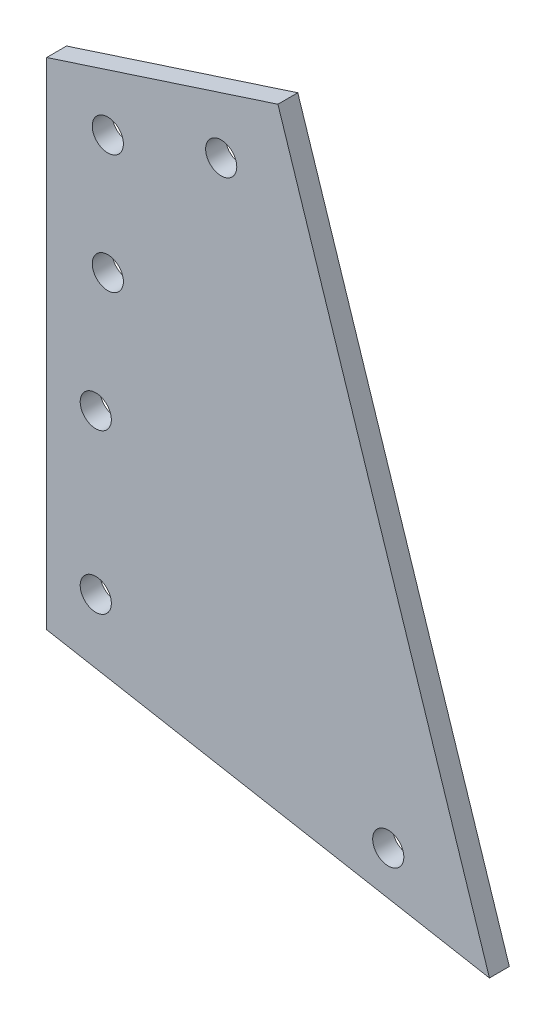
SolidWorks part; units mm, degrees
material "6061 Alloy"
ref_plane "Front Plane" through (0, 0, 0) normal (0, 0, 1) x (1, 0, 0)
ref_plane "Top Plane" through (0, 0, 0) normal (0, 1, 0) x (1, 0, 0)
ref_plane "Right Plane" through (0, 0, 0) normal (1, 0, 0) x (0, 0, -1)
sketch "Sketch2" plane through (0, 0, 0) normal (0, 0, 1) x (1, 0, 0)
  line L0 (40.9906, 297.6036) -> (41.8047, 295.0986) construction
  line L2 (40.9906, 297.6036) -> (52.5693, 261.9727) construction
  line L6 (197.5978, -184.3191) -> (40.9906, 297.6036) construction
  line L7 (75.6055, 191.0842) -> (41.8047, 295.0986)
  line L8 (4.8542, 283.091) -> (4.8542, 203.9015)
  line L9 (4.8542, 203.9015) -> (75.6055, 191.0842)
  line L10 (12.7, 238.125) -> (12.7, 212.725) construction
  line L11 (52.3134, 180.5741) -> (64.7523, 184.6158) construction
  line L12 (173.4413, -192.1691) -> (25.4, 263.394) construction
  line L13 (64.7523, 184.6158) -> (29.6, 292.8012) construction
  line L14 (41.8047, 295.0986) -> (4.8542, 283.091)
  dimension "D1" = 109.3686
extrude "Boss-Extrude1" add sketch "Sketch2" along normal blind 3.175
sketch "Sketch3" plane through (0, 0, 3.175) normal (0, 0, 1) x (1, 0, 0)
  line L0 (75.6055, 191.0842) -> (63.8877, 187.2769) construction
  line L1 (63.8877, 187.2769) -> (29.6006, 292.8015) construction
  line L3 (61.8403, 193.5779) -> (59.4352, 200.9803) construction
  line L4 (4.8542, 203.9015) -> (75.6055, 191.0842) construction
  line L5 (29.6006, 292.8015) -> (32.7403, 283.1387) construction
  line L6 (32.7403, 283.1387) -> (14.6226, 277.2519) construction
  line L7 (14.6226, 277.2519) -> (14.6226, 258.2019) construction
  dimension "D1" = 86.3865
hole_wizard "#10 Clearance Hole1" positions "Sketch4" profile "Sketch5" hole size "#10" standard "ANSI Inch" end condition through all
sketch "Sketch4" plane through (0, 0, 3.175) normal (0, 0, 1) x (1, 0, 0)
  point P0 (32.7403, 283.1387)
  point P3 (59.4352, 200.9803)
  point P7 (12.7, 238.125)
  point P10 (12.7, 212.725)
  point P14 (14.6226, 277.2519)
  point P17 (14.6226, 258.2019)
sketch "Sketch5" plane through (32.7403, 283.1387, 3.175) normal (1, 0, 0) x (0, -1, 0)
  line L0 (0, 0) -> (0, 3.175)
  line L1 (0, 3.175) -> (2.4892, 3.175)
  line L2 (2.4892, 3.175) -> (2.4892, 0)
  line L5 (2.4892, 0) -> (0, 0)
  line L11 (0, -6.35) -> (0, 107.95) construction
  dimension "Thru Hole Dia." = 4.9784
  dimension "Thru Hole Depth" = 3.175
